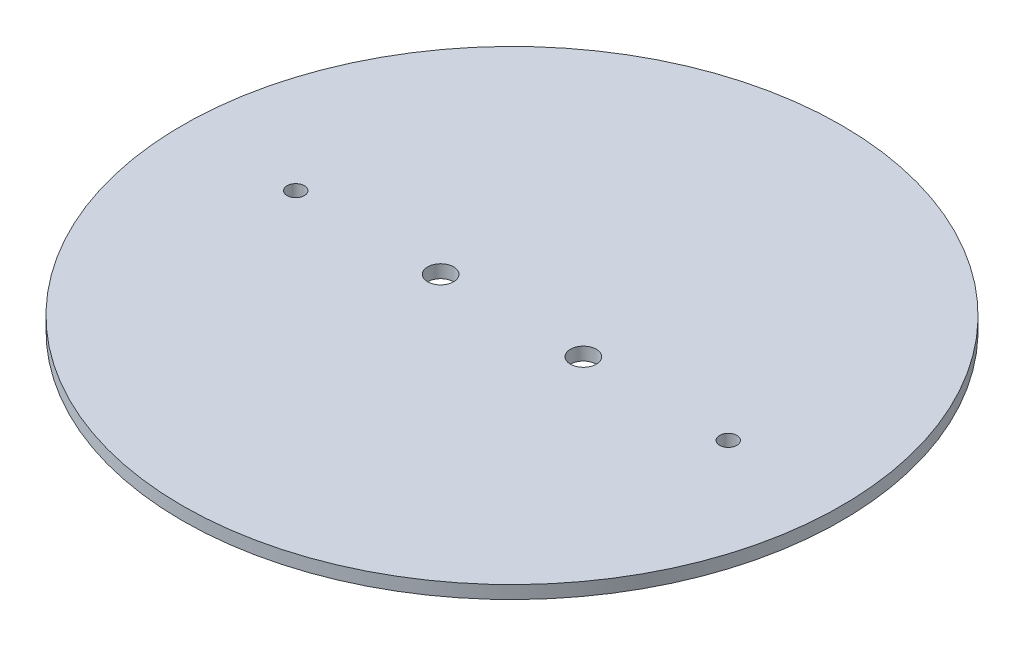
SolidWorks part; units mm, degrees
material "1060 Alloy"
ref_plane "Front Plane" through (0, 0, 0) normal (0, 0, 1) x (1, 0, 0)
ref_plane "Top Plane" through (0, 0, 0) normal (0, 1, 0) x (1, 0, 0)
ref_plane "Right Plane" through (0, 0, 0) normal (1, 0, 0) x (0, 0, -1)
sketch "Sketch1" plane through (0, 0, 0) normal (0, 1, 0) x (1, 0, 0)
  line L0 (-50, 0) -> (50, 0) construction
  circle A0 centre (0, 0) radius 76.2
  circle A1 centre (-50, 0) radius 2
  circle A2 centre (50, 0) radius 2
  circle A3 centre (-16.5, 0) radius 3
  circle A4 centre (16.5, 0) radius 3
  dimension "D1" = 152.4
  dimension "D2" = 4
  dimension "D3" = 4
  dimension "D5" = 6
  dimension "D6" = 6
  dimension "D4" = 100
  dimension "D7" = 16.5
  dimension "D8" = 16.5
extrude "Boss-Extrude1" add sketch "Sketch1" along normal blind 1.5 and the other way blind 1.5
